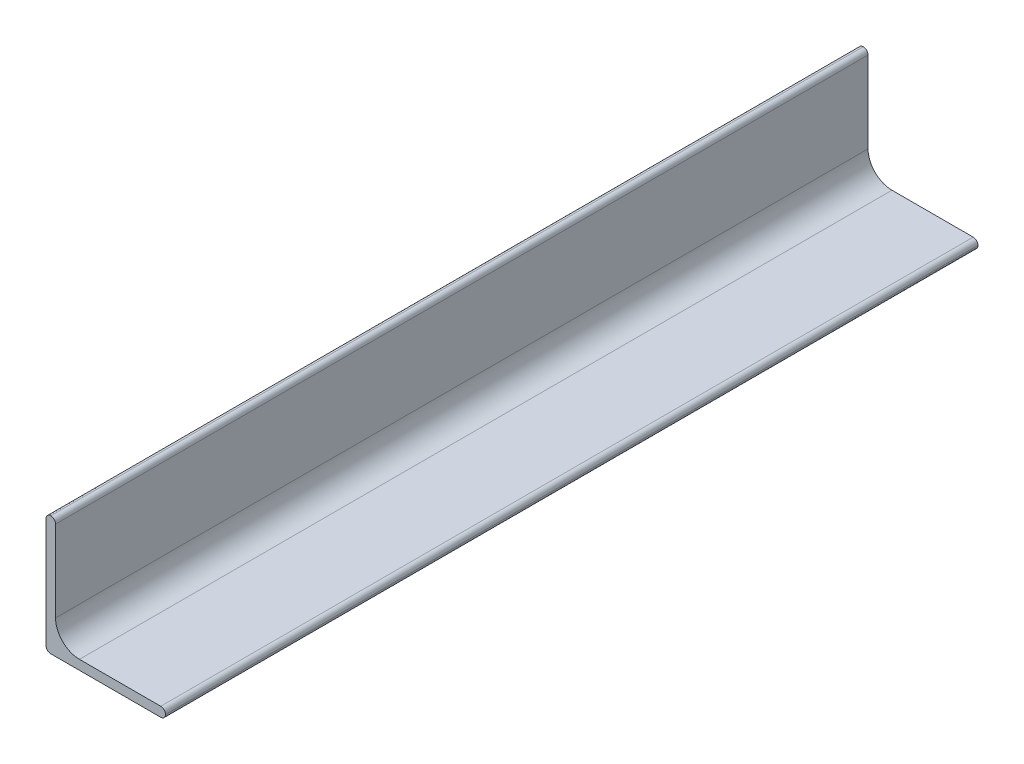
SolidWorks part; units mm, degrees
material "Q235锻制"
ref_plane "前视基准面" through (0, 0, 0) normal (0, 0, 1) x (1, 0, 0)
ref_plane "上视基准面" through (0, 0, 0) normal (0, 1, 0) x (1, 0, 0)
ref_plane "右视基准面" through (0, 0, 0) normal (1, 0, 0) x (0, 0, -1)
sketch "草图1" plane through (0, 0, 0) normal (0, 0, 1) x (1, 0, 0)
  line L0 (0, 0) -> (25, 0)
  line L1 (55, 0) -> (-55, 0) construction
  line L2 (25, 0) -> (25, 2)
  line L3 (25, 2) -> (7, 2)
  line L4 (2, 7) -> (2, 25)
  line L5 (2, 25) -> (0, 25)
  line L6 (0, -55) -> (0, 55) construction
  line L7 (0, 25) -> (0, 0)
  arc A0 (7, 2) -> (2, 7) centre (7, 7) cw
  dimension "D5" = 5
  dimension "D1" = 25
  dimension "D2" = 25
  dimension "D3" = 2
  dimension "D4" = 2
extrude "凸台-拉伸1" add sketch "草图1" along normal blind 170
fillet "圆角1" radius 1 5 edges at (0, 25, 85) (25, 2, 85) (25, 0, 85) (0, 0, 85) (2, 25, 85)
